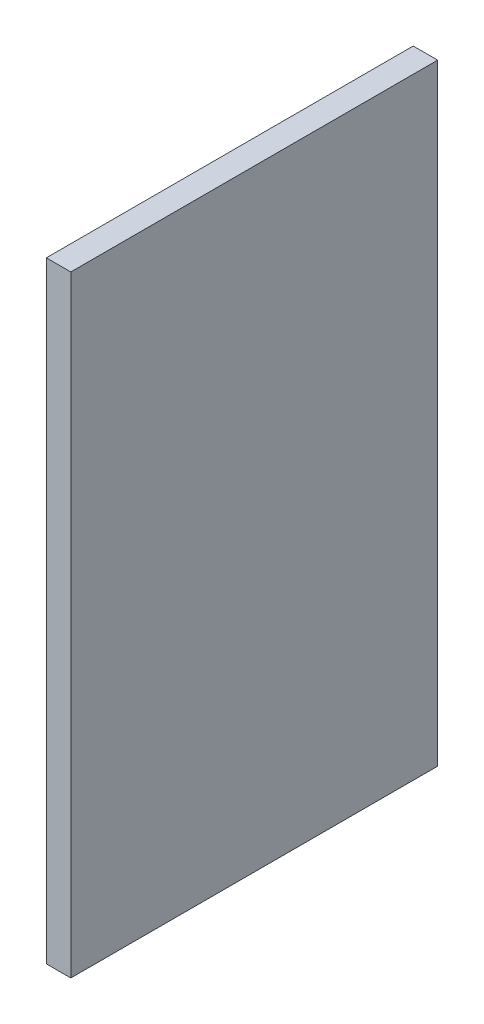
SolidWorks part; units mm, degrees
ref_plane "前视基准面" through (0, 0, 0) normal (0, 0, 1) x (1, 0, 0)
ref_plane "上视基准面" through (0, 0, 0) normal (0, 1, 0) x (1, 0, 0)
ref_plane "右视基准面" through (0, 0, 0) normal (1, 0, 0) x (0, 0, -1)
other "Configuration Table"
sketch "草图1" plane through (0, 0, 0) normal (0, 1, 0) x (1, 0, 0)
  line L1 (-110, -38) -> (-109.2, -38)
  line L2 (-110, -38) -> (-110, -26)
  line L3 (-110, -26) -> (-109.2, -26)
  line L4 (-109.2, -38) -> (-109.2, -26)
extrude "Mating_patch_20x12x0p8" add sketch "草图1" along normal blind 10 and the other way blind 10
